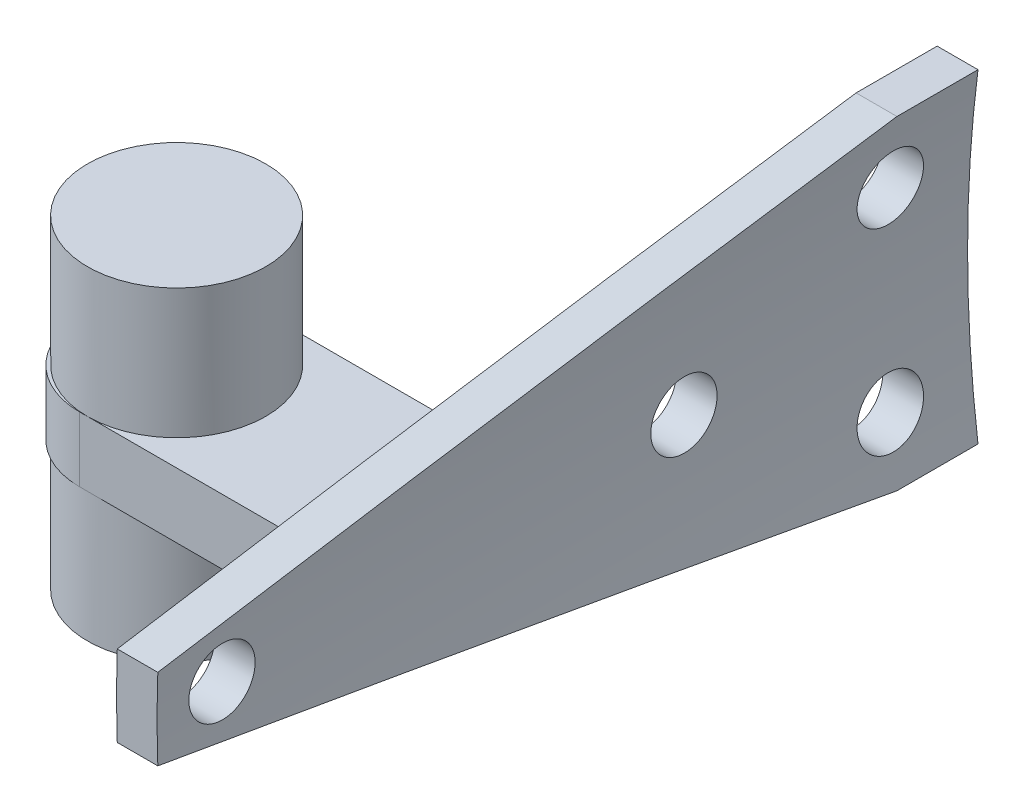
SolidWorks part; units mm, degrees
material "Plain Carbon Steel"
ref_plane "Front Plane" through (0, 0, 0) normal (0, 0, 1) x (1, 0, 0)
ref_plane "Top Plane" through (0, 0, 0) normal (0, 1, 0) x (1, 0, 0)
ref_plane "Right Plane" through (0, 0, 0) normal (1, 0, 0) x (0, 0, -1)
sketch "Sketch1" plane through (0, 0, 0) normal (0, 0, 1) x (1, 0, 0)
  line L0 (0, 0) -> (-52.4035, 0) construction
  line L1 (-80.078, 10) -> (-77.558, 10)
  line L2 (-80.078, -10) -> (-77.558, -10)
  arc A0 (-77.558, 10) -> (-77.558, -10) centre (0, 0) ccw
  arc A1 (-80.078, 10) -> (-80.078, -10) centre (0, 0) ccw
  dimension "D2" = 78.2
  dimension "D1" = 2.5
  dimension "D3" = 20
extrude "Boss-Extrude1" add sketch "Sketch1" along normal blind 50
sketch "Sketch2" plane through (0, 0, 0) normal (1, 0, 0) x (0, 0, -1)
  line L0 (0, 10) -> (0, -10)
  line L1 (0, 10) -> (-50, 10) construction
  line L2 (0, 10) -> (0, -10) construction
  line L3 (0, -10) -> (-50, -10) construction
  line L4 (-50, 10) -> (-50, -10) construction
  line L5 (0, -10) -> (-5, -10)
  line L6 (-5, -10) -> (-50, -2.5)
  line L7 (-50, -2.5) -> (-50, 2.5)
  line L8 (-50, 2.5) -> (-5, 10)
  line L9 (-5, 10) -> (0, 10)
  line L10 (0, 0) -> (-50.031, 0) construction
  line L12 (-88.7937, 27.6855) -> (20.3533, 27.6855)
  line L13 (-88.7937, 27.6855) -> (-88.7937, -33.0502)
  line L14 (-88.7937, -33.0502) -> (20.3533, -33.0502)
  line L15 (20.3533, 27.6855) -> (20.3533, -33.0502)
  dimension "D1" = 5
extrude "Cut-Extrude1" cut sketch "Sketch2" against normal through all
hole_wizard "#20 (0.161) Diameter Hole1" positions "Sketch5" profile "Sketch4" hole size "#20" standard "ANSI Inch" end condition through all
sketch "Sketch5" plane through (0, 0, 0) normal (1, 0, 0) x (0, 0, -1)
  line L1 (0, -10) -> (-42.3856, -10)
  line L2 (0, -10) -> (0, 10)
  line L3 (0, 10) -> (-42.3856, 10)
  line L4 (-42.3856, -10) -> (-42.3856, 10)
  line L7 (-5, 10) -> (0, 10) construction
  line L8 (0, 0) -> (-42.3856, 0)
  line L10 (-5, 6) -> (-5, -6)
  line L11 (-50, 2.5) -> (-50, -2.5) construction
  point P0 (-46, 0)
  point P164 (-5, 6)
  point P165 (-5, -6)
  point P172 (-5, 0)
  point P177 (-17.5, 0)
  dimension "D1" = 5
  dimension "D2" = 4
  dimension "D3" = 4
  dimension "D4" = 12.5
sketch "Sketch4" plane through (0, 0, 46) normal (0, 1, 0) x (0, 0, -1)
  line L0 (0, 0) -> (0, 80.7)
  line L1 (0, 80.7) -> (2.0447, 80.7)
  line L2 (2.0447, 80.7) -> (2.0447, 0)
  line L5 (2.0447, 0) -> (0, 0)
  line L11 (0, -6.35) -> (0, 107.95) construction
  dimension "Thru Hole Dia." = 4.0894
  dimension "Thru Hole Depth" = 80.7
ref_plane "Plane1" through (-80, 0, 0) normal (1, 0, 0) x (0, 0, -1)
sketch "Sketch7" plane through (-80, 0, -87.9998) normal (1, 0, 0) x (0, 0, -1)
  line L0 (-87.9998, 0) -> (-80.3469, 0) construction
  line L1 (-125.9998, 2) -> (-114.9998, 2)
  line L2 (-125.9998, 2) -> (-125.9998, -2)
  line L3 (-125.9998, -2) -> (-114.9998, -2)
  line L4 (-114.9998, 2) -> (-114.9998, -2)
  line L5 (-87.9998, 10) -> (-87.9998, -10) construction
  line L6 (-87.9998, -10) -> (-87.9998, 10) construction
  circle A2 centre (-133.9998, 0) radius 2.0447 construction
  point P8 (-125.9998, 0)
  dimension "D2" = 11
  dimension "D1" = 4
  dimension "D3" = 8
extrude "Boss-Extrude2" add sketch "Sketch7" against normal blind 20
fillet "Fillet1" radius 2 4 edges at (-80.6752, 2, 32.5) (-80.7, 0, 38) (-80.7, 0, 27) (-80.6752, -2, 32.5)
sketch "Sketch8" plane through (0, -2, 0) normal (0, -1, 0) x (1, 0, 0)
  line L1 (-89, 27) -> (-100, 27) construction
  line L2 (-89, 27) -> (-89, 38) construction
  line L3 (-89, 38) -> (-100, 38) construction
  line L4 (-100, 27) -> (-100, 38) construction
  line L5 (-89, 27) -> (-100, 38) construction
  line L6 (-89, 38) -> (-100, 27) construction
  circle A0 centre (-94.5, 32.5) radius 5.5
  point P0 (-94.5, 32.5)
extrude "Boss-Extrude3" add sketch "Sketch8" along normal blind 8 and the other way blind 12
fillet "Fillet2" radius 5 2 edges at (-100, 0, 38) (-100, 0, 27)
equation "\"TubeDiameter\"= 6.000in"
equation "\"D2@Sketch1\"=\"TubeDiameter\"/2+2mm"
